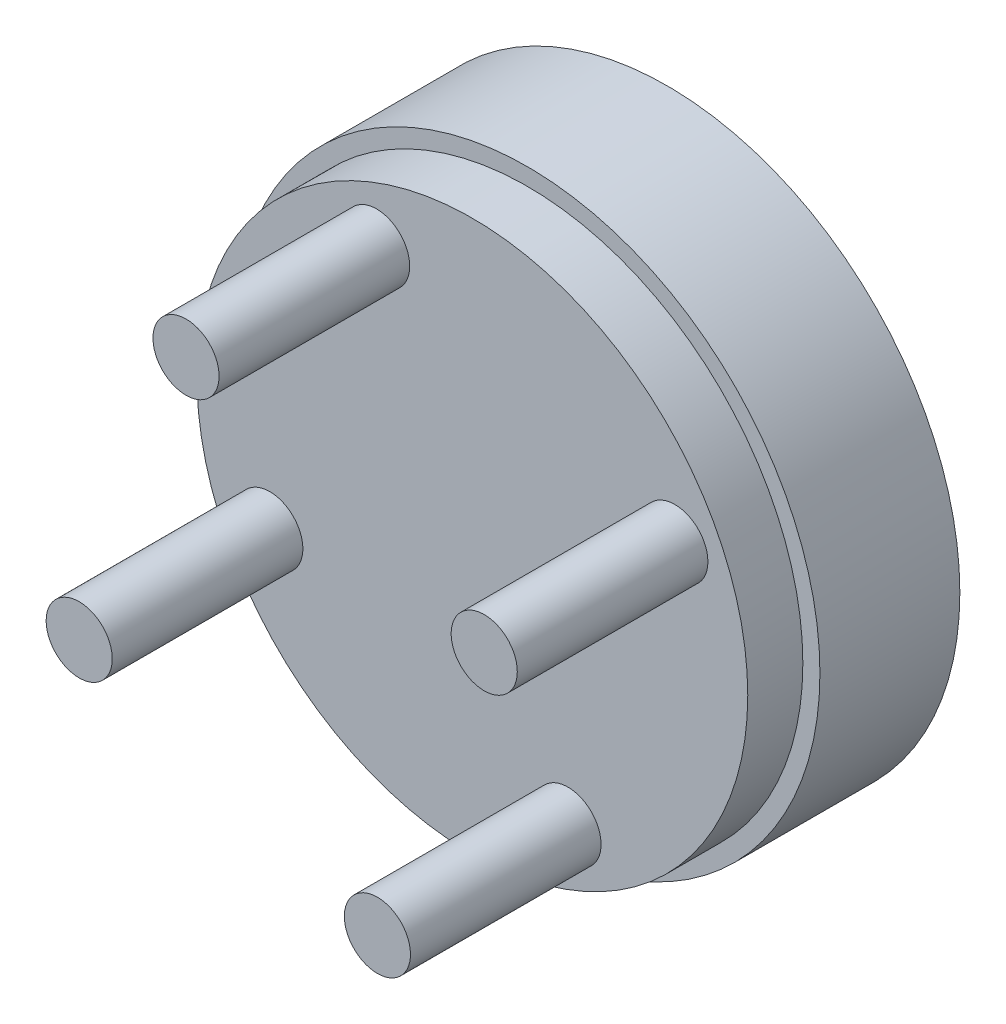
SolidWorks part; units mm, degrees
ref_plane "Plan de face" through (0, 0, 0) normal (0, 0, 1) x (1, 0, 0)
ref_plane "Plan de dessus" through (0, 0, 0) normal (0, 1, 0) x (1, 0, 0)
ref_plane "Plan de droite" through (0, 0, 0) normal (1, 0, 0) x (0, 0, -1)
sketch "Esquisse1" plane through (0, 0, 0) normal (0, 0, 1) x (1, 0, 0)
  circle A0 centre (0, 0) radius 53.1
  dimension "D1" = 106.2
extrude "Boss.-Extru.1" add sketch "Esquisse1" along normal blind 25.4
sketch "Esquisse2" plane through (0, 0, 25.4) normal (0, 0, 1) x (1, 0, 0)
  circle A0 centre (0, 0) radius 50
  dimension "D1" = 100
extrude "Boss.-Extru.2" add sketch "Esquisse2" along normal blind 10
sketch "Esquisse3" plane through (0, 0, 35.4) normal (0, 0, 1) x (1, 0, 0)
  circle A0 centre (36.7631, 17.3699) radius 6
  point P2 (0, 0)
  dimension "D2" = 12
  dimension "D1" = 40.66
extrude "Boss.-Extru.3" add sketch "Esquisse3" along normal blind 34.6
ref_axis "Axe1" through (0, 0, 25.4) along (0, 0, -1)
pattern_circular "Répétition circulaire1" count 4 every 90 about axis through (0, 0, 25.4) along (0, 0, -1) of "Boss.-Extru.3"
equation "\"holeD\"= 12"
equation "\"D2@Esquisse3\"=\"holeD\""
equation "\"gearEpis\"= 34.6"
equation "\"D1@Boss.-Extru.3\"=\"gearEpis\""
